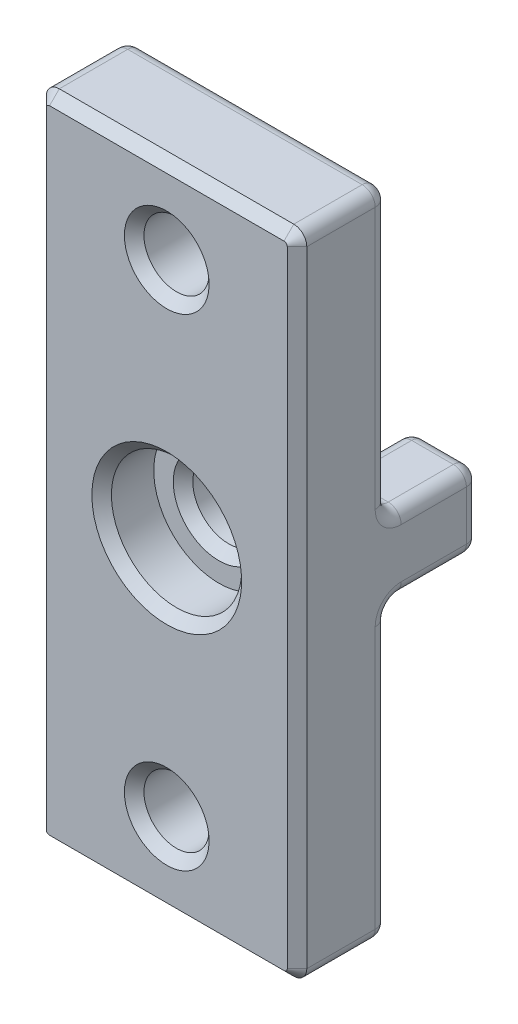
SolidWorks part; units mm, degrees
ref_plane "Спереди" through (0, 0, 0) normal (0, 0, 1) x (1, 0, 0)
ref_plane "Сверху" through (0, 0, 0) normal (0, 1, 0) x (1, 0, 0)
ref_plane "Справа" through (0, 0, 0) normal (1, 0, 0) x (0, 0, -1)
other "Configuration Table"
sketch "Эскиз2" plane through (0, 0, 0) normal (0, 0, 1) x (1, 0, 0)
  line L20 (-3, 10) -> (-8.5, 10) construction
  line L21 (0, 10) -> (0, 4.8) construction
  line L24 (3, 4.5) -> (-3, 4.5) construction
  line L79 (-2.9, 10) -> (-2.9, 4.8)
  line L80 (-2.9, 4.8) -> (2.9, 4.8)
  line L81 (2.9, 4.8) -> (2.9, 10)
  line L114 (-2.9, 10) -> (2.9, 10)
  line L116 (10, 2.9) -> (4.8, 2.9)
  line L117 (4.8, 2.9) -> (4.8, -2.9)
  line L118 (4.8, -2.9) -> (10, -2.9)
  line L119 (10, 2.9) -> (10, -2.9)
  line L120 (2.9, -10) -> (2.9, -4.8)
  line L121 (2.9, -4.8) -> (-2.9, -4.8)
  line L122 (-2.9, -4.8) -> (-2.9, -10)
  line L123 (2.9, -10) -> (-2.9, -10)
  line L124 (-10, -2.9) -> (-4.8, -2.9)
  line L125 (-4.8, -2.9) -> (-4.8, 2.9)
  line L126 (-4.8, 2.9) -> (-10, 2.9)
  line L127 (-10, -2.9) -> (-10, 2.9)
  point P3 (0, 4.5)
  point P30 (0, 0)
  dimension "D2" = 4
  dimension "D3" = 5.8
  dimension "D1" = 0.3
extrude "Бобышка-Вытянуть1" add sketch "Эскиз2" against normal blind 7 contours L118 L119 L116 L117 | L121 L122 L123 L120 | L124 L125 L126 L127 | L80 L81 L114 L79
sketch "Эскиз3" plane through (0, 0, 0) normal (0, 0, 1) x (1, 0, 0)
  line L0 (-10, -3) -> (-10, -8.5) construction
  line L1 (10, -8.5) -> (10, -3) construction
  line L3 (-10, 24) -> (-10, -24)
  line L4 (10, -24) -> (10, 24)
  line L6 (-9, 25) -> (9, 25)
  line L7 (-9, -25) -> (9, -25)
  line L8 (-3, 10) -> (-8.5, 10) construction
  line L9 (-8.5, -10) -> (-3, -10) construction
  line L10 (-10, 0) -> (10, 0) construction
  circle A1 centre (0, 0) radius 2.75
  arc A4 (-10, 24) -> (-9, 25) centre (-9, 24) cw
  arc A5 (9, 25) -> (10, 24) centre (9, 24) cw
  arc A6 (-10, -24) -> (-9, -25) centre (-9, -24) ccw
  arc A7 (9, -25) -> (10, -24) centre (9, -24) ccw
  circle A9 centre (0, 18.5) radius 2.5
  circle A11 centre (0, -18.5) radius 2.5
  point P21 (0, 25)
  dimension "D1" = 1
  dimension "D4" = 5
  dimension "D5" = 4
  dimension "D6" = 5.5
  dimension "D2" = 15
  dimension "D3" = 15
extrude "Бобышка-Вытянуть2" add sketch "Эскиз3" along normal blind 7
fillet "Скругление1" radius 1 59 edges at (7.4, -2.9, 0) (7.4, 2.9, 0) (-7.4, 2.9, 0) (-7.4, -2.9, 0) (4.8, -2.9, -3.5) (4.8, 2.9, -3.5) (4.8, 0, 0) (-2.9, 7.4, 0) (-2.9, 10, -3.5) (0, 10, 0) (2.9, 10, -3.5) (2.9, 7.4, 0) (2.9, 4.8, -3.5) (-2.9, 4.8, -3.5) (0, 4.8, 0) (-4.8, 2.9, -3.5) (-4.8, -2.9, -3.5) (-4.8, 0, 0) (-2.9, -7.4, 0) (-2.9, -4.8, -3.5) (0, -4.8, 0) (2.9, -4.8, -3.5) (2.9, -7.4, 0) (2.9, -10, -3.5) (-2.9, -10, -3.5) (0, -10, 0) (0, -4.8, -7) (-2.9, -7.4, -7) (0, -10, -7) (2.9, -7.4, -7) (-7.4, -2.9, -7) (-4.8, 0, -7) (-7.4, 2.9, -7) (-10, 0, -7) (0, 4.8, -7) (2.9, 7.4, -7) (0, 10, -7) (-2.9, 7.4, -7) (7.4, -2.9, -7) (10, 0, -7) (7.4, 2.9, -7) (4.8, 0, -7) (-10, -2.9, -3.5) (10, -2.9, -3.5) (10, 2.9, -3.5) (-10, 2.9, -3.5) (-2.5, -18.5, 0) (2.5, 18.5, 0) (-10, -13.45, 0) (-9.7071, -24.7071, 0) (0, -25, 0) (9.7071, -24.7071, 0) (10, -13.45, 0) (10, 13.45, 0) (9.7071, 24.7071, 0) (0, 25, 0) (-9.7071, 24.7071, 0) (-10, 13.45, 0) (2.75, 0, 0)
sketch "Эскиз5" plane through (0, 0, 7) normal (0, 0, 1) x (1, 0, 0)
  circle A0 centre (0, 0) radius 5
  dimension "D1" = 10
extrude "Вырез-Вытянуть2" cut sketch "Эскиз5" against normal blind 4
chamfer "Фаска1" distance 0.75 angle 45 12 edges at (-2.5, -18.5, 7) (2.5, 18.5, 7) (0, 25, 7) (9.7071, 24.7071, 7) (10, 0, 7) (9.7071, -24.7071, 7) (0, -25, 7) (-9.7071, -24.7071, 7) (-10, 0, 7) (-9.7071, 24.7071, 7) (5, 0, 7) (2.75, 0, 3)
